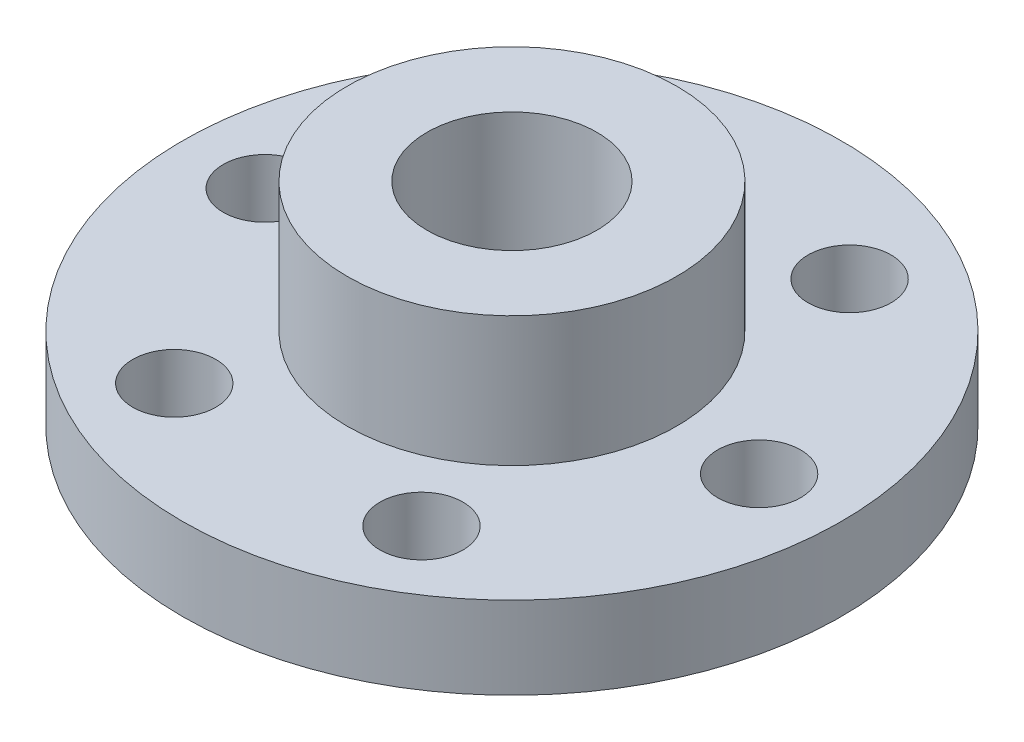
SolidWorks part; units mm, degrees
ref_plane "Front Plane" through (0, 0, 0) normal (0, 0, 1) x (1, 0, 0)
ref_plane "Top Plane" through (0, 0, 0) normal (0, 1, 0) x (1, 0, 0)
ref_plane "Right Plane" through (0, 0, 0) normal (1, 0, 0) x (0, 0, -1)
sketch "Sketch1" plane through (0, 0, 0) normal (0, 1, 0) x (1, 0, 0)
  line L0 (0, 0) -> (6.5484, 0) construction
  line L4 (0, 0) -> (-19.05, 0) construction
  circle A0 centre (0, 0) radius 4.826
  circle A1 centre (0, 0) radius 6.5484 construction
  arc A2 (3.9286, 10.8597) -> (3.9286, -10.8597) centre (0, 0) ccw construction
  circle A3 centre (0, 0) radius 25.4
  circle A5 centre (0, 0) radius 11.5484 construction
  circle A6 centre (-19.05, 0) radius 2.9766 construction
  dimension "D1" = 9.652
  dimension "D2" = 13.0969
  dimension "D3" = 23.0969
  dimension "D7" = 5.9531
  dimension "D5" = 50.8
  dimension "D4" = 19.05
extrude "main body" add sketch "Sketch1" along normal blind 6.35
sketch "Sketch2" plane through (0, 6.35, 0) normal (0, 1, 0) x (1, 0, 0)
  circle A0 centre (0, 0) radius 12.7
  circle A2 centre (0, 0) radius 6.5484
  dimension "D1" = 13.0969
  dimension "D2" = 25.4
extrude "tap boss" add sketch "Sketch2" along normal blind 10
hole_wizard "M6 Clearance Hole1" positions "Sketch3" profile "Sketch4" hole size "M6" standard "ANSI Metric" end condition through all
sketch "Sketch3" plane through (0, 6.35, 0) normal (0, 1, 0) x (1, 0, 0)
  point P0 (-19.05, 0)
  point P7 (-9.525, 16.4978)
  point P8 (9.525, 16.4978)
  point P9 (19.05, 0)
  point P10 (9.525, -16.4978)
  point P11 (-9.525, -16.4978)
  point P12 (0, 0)
  dimension "D1" = 6
sketch "Sketch4" plane through (-19.05, 6.35, 0) normal (1, 0, 0) x (0, 0, 1)
  line L0 (0, 0) -> (0, 6.35)
  line L1 (0, 6.35) -> (3.2, 6.35)
  line L2 (3.2, 6.35) -> (3.2, 0)
  line L5 (3.2, 0) -> (0, 0)
  line L11 (0, -6.35) -> (0, 107.95) construction
  dimension "Thru Hole Dia." = 6.4
  dimension "Thru Hole Depth" = 6.35
sketch "Sketch5" plane through (0, 0, 0) normal (0, -1, 0) x (1, 0, 0)
  line L0 (0, 0) -> (-25.4, 0) construction
  line L1 (-25.4, 0) -> (-25.4, 25.4) construction
  line L2 (-25.4, 25.4) -> (0, 25.4) construction
  line L3 (0, 25.4) -> (0, 0) construction
  circle A0 centre (0, 0) radius 25.4 construction
equation "\"z\" = 8\t\t\t\t'number of blades"
equation "\"de\" = 0.43in\t\t\t'entrance eye diameter"
equation "\"de_length\" = 4mm\t\t'entrance eye consistent length"
equation "\"d_exit\" = 0.18in \t\t'throat aka d1"
equation "\"d2\" = 2.1in \t\t\t'outer diameter of the impeller"
equation "\"b2\" = .2in\t\t\t'tip height from disc surface at d2; slightly higher than d_exit"
equation "\"b1\" = \"b2\" + (\"d2\"/2 - \"de\"/2)*tan(\"theta\") \t\t\t'tip height from disc surface at inlet eye"
equation "\"theta\" = 12\t\t\t'angle of blades from inner to outer "
equation "\"ae\" = 3.14*(\"de\"^2)/4\t\t'entrance eye area'"
equation "\"ce\" = 3.14*\"de\"\t\t'entrance eye circumference"
equation "\"av_ratio\" = .325\t\t'ratio of av/ae at N_s of 470, range is .275 to .375, .325 ideal. High ratio means bigger area means smaller blades"
equation "\"av\" = \"ae\"*\"av_ratio\"\t\t'area between just two blades"
equation "\"s_open\" = \"av\"/\"b1\"\t\t'width of open area"
equation "\"s\"=\"ce\" - \"z\"*\"s_open\""
equation "\"min blade thickness\" = .15in"
equation "\"bearing OD\" = 30mm"
equation "\"bearing ID\"= 10mm"
equation "\"bearing depth\"= 9mm"
equation "\"bearing outer race thickness\"= 1mm"
equation "\"bearing inner race thickness\"= 1mm"
equation "\"bearing bore\" = \"bearing depth\" + 1mm"
equation "\"lower seal OD\" = .917in\t\t'this is https://www.mcmaster.com/#9281k121/=174001b"
equation "\"lower seal ID\"= .375in"
equation "\"lower seal depth\" = .625in + .218in"
equation "\"lower seal bore\" = \"lower seal depth\" + 1mm"
equation "\"upper seal OD\" = 1.125in\t'this is https://www.mcmaster.com/#5154t33/=173zuau, needs to be visually inspected before machining!"
equation "\"upper seal ID\"= 0.625in"
equation "\"upper seal depth\"= .25in\t'aka height; these values need to be confirmed by inspection!! We may want to compress the height."
equation "\"upper seal bore\" = \"upper seal depth\" + 1mm"
equation "\"big o-ring thickness\" = .139in"
equation "\"big o-ring OD\" = 2.734in"
equation "\"big o-ring ID\" = 3.012in"
equation "\"big o-ring groove depth\" = \"big o-ring thickness\"*4/5"
equation "\"impeller center height\" = \"impeller base thickness\" + \"b1\"\t'impeller height at de"
equation "\"impeller outer height\" = \"impeller base thickness\" + \"b2\"\t'impeller height at de"
equation "\"impeller upper clearance\"= .5mm"
equation "\"impeller horizontal clearance\"= (\"d2\"*1.15 - \"d2\")/2 \t\t'clearance based on D2-D3 ratio for circular volute, ranges 1.15 to 1.2"
equation "\"impeller bottom clearance\"= .5mm"
equation "\"impeller base thickness\"= 2mm"
equation "\"impeller dowel diameter\" = 2mm"
equation "\"impeller bolt head diameter\" = \"m4 head bore diameter\""
equation "\"impeller bolt head depth\" = 4mm"
equation "\"impeller bolt stop depth\" = 3mm"
equation "\"impeller bolt bore\" = \"m4 clearance\""
equation "\"impeller shaft bore depth\" = 12mm"
equation "\"impeller shaft bore\" = 8mm"
equation "\"impeller boss depth\" = \"impeller shaft bore depth\"+\"impeller bolt stop depth\"+\"impeller bolt head depth\"-\"impeller base thickness\""
equation "\"impeller boss diameter\" = \"upper seal ID\""
equation "\"impeller dowel length\" = 2mm*2 + \"impeller shaft bore\""
equation "\"coupler motor shaft hole ID\"= 8mm"
equation "\"coupler OD\"= 17mm"
equation "\"coupler length\"= 25mm"
equation "\"motor OD\" = 64mm"
equation "\"motor shaft diameter\"= 8mm"
equation "\"motor shaft pride\"= 32mm"
equation "\"motor to bearing plate distance\" = \"motor shaft pride\" + 2mm +\"coupler length\"/2"
equation "\"square plate bolt bore\" = \"m8 clearance\""
equation "\"square plate bolt head diameter\" = 13.5mm"
equation "\"square plate bolt head depth\" = 8mm"
equation "\"square plate bolt pattern diameter\"= 3.5in"
equation "\"motor mount center bore\"= \"coupler OD\"+ 4mm"
equation "\"motor mount post radius\"= ( 3 * \"square plate bolt bore\" ) / 2"
equation "\"motor mount m4 screw hole diameter\"= 4mm"
equation "\"motor mount m4 head diameter\"= 7.25mm"
equation "\"motor mount m4 head depth\"= 4mm"
equation "\"motor mount m4 pattern diamater\" = 30mm"
equation "\"motor mount plate thickness\"= 8mm + \"motor mount m4 head depth\""
equation "\"bearing plate stop ID\" = \"bearing OD\" - 4mm"
equation "\"bearing plate stop depth\" = 3mm"
equation "\"bearing plate thickness\" = \"bearing bore\" + \"bearing plate stop depth\" + \"shaft bearing stop length\""
equation "\"lower seal plate lip depth\" = 2mm"
equation "\"lower seal plate lip ID\" = \"lower seal OD\" - 3mm"
equation "\"lower seal plate thickness\" = \"lower seal plate lip depth\" + \"lower seal bore\""
equation "\"shaft coupler section diameter\" = 8mm"
equation "\"shaft coupler section length\" = \"motor to bearing plate distance\" - \"motor shaft pride\" - 2mm"
equation "\"shaft bearing section diameter\" = \"bearing ID\""
equation "\"shaft bearing section length\" = \"bearing plate stop depth\" + \"bearing depth\""
equation "\"shaft bearing stop diameter\" = \"bearing ID\" + 4mm"
equation "\"shaft bearing stop length\" = 3mm"
equation "\"shaft lower seal section diameter\" = \"lower seal ID\""
equation "\"shaft lower seal section length\" = \"lower seal plate thickness\" + 1mm"
equation "\"shaft impeller section diameter\" = \"impeller shaft bore\""
equation "\"shaft impeller section length\" = \"upper seal plate thickness\" + \"upper seal plate riser\" + \"impeller bottom clearance\" + \"impeller base thickness\" - \"impeller bolt head depth\" - \"impeller bolt stop depth\""
equation "\"upper seal plate thickness\" = \"upper seal plate pressure hole diameter\"+10mm"
equation "\"upper seal plate lip ID\" = \"upper seal OD\" - 3mm"
equation "\"upper seal plate riser\" = 6.59mm \t\t'this number needs to be read from the housing file"
equation "\"upper seal plate pressure hole diameter\" = .125in\t'this is 1/8 drill "
equation "\"upper seal plate pressure tap diameter\" = .328125in \t'this is 21/64 drill for a 1/8 ANPT tap"
equation "\"upper seal plate pressure tap grip\" = 5mm\t\t'this is the area around the tap so it doesn't crack"
equation "\"upper seal plate pressure tap depth\" = 12mm"
equation "\"impeller cavity center height\"= \"impeller bottom clearance\" + \"impeller upper clearance\" + \"impeller center height\""
equation "\"impeller cavity diameter\"= 2 * \"impeller horizontal clearance\" + \"d2\" \t\t\t\t\t\t\t\t\t'called D3 analytically"
equation "\"impeller cavity outer height\"= \"impeller bottom clearance\" + \"impeller upper clearance\" + \"impeller base thickness\" + \"b2\" \t\t'this is height at impeller diameter d2, not at d3"
equation "\"impeller housing thickness\"= \"impeller housing exit threaded diameter\" + 2*\"impeller housing outlet grip\""
equation "\"impeller housing diameter\" = 4.5in"
equation "\"impeller housing bolt count\" = 8"
equation "\"impeller housing bolt diameter\" = \"m6 clearance\""
equation "\"impeller housing bolt pattern diameter\" = 3.5in"
equation "\"impeller housing threaded inlet diameter\" = 0.71875in \t'this is the 23/32 drill size for 1/2 NPT fitting https://www.mcmaster.com/#50715k269/=176pljy"
equation "\"impeller housing threaded inlet depth\"= .6in"
equation "\"impeller housing exit threaded diameter\"= 0.515625in \t\t'this is the 33/64 drill size for 9/16-18 fitting, expecting swagelok SS-8FK0-1-6STH fitting"
equation "\"impeller housing exit threaded depth\"= 10mm"
equation "\"impeller housing diffuser conical angle\"=10"
equation "\"impeller housing diffuser tangent angle\"=5"
equation "\"impeller housing diffuser final diameter\" = .38in\t\t'aka d2'"
equation "\"impeller housing outlet grip\" = 5mm"
equation "\"end mill size\" = 0.375in\t'for 3/8 endmill"
equation "\"m4 clearance\" = 0.171875in \t'this is 11/64 bit for 4.36mm"
equation "\"m4 tap\" = 0.125in\t\t'this is 1/8 bit for 3.17mm"
equation "\"m4 head bore diameter\" = 7.5mm"
equation "\"m4 head bore depth\" = 5mm\t'actual is ~4mm"
equation "\"m6 clearance\" = 0.234375in\t'this is 15/64 bit = 5.95mm, could use 6mm bit, B bit for 6.04mm or 1/4 bit for 6.35mm"
equation "\"m6 tap\" = 5mm\t\t\t'5mm is appropriate, could use 13/64 or #5,6,7"
equation "\"m6 head bore diameter\" = 11mm\t\t"
equation "\"m6 head bore depth\" = 7mm\t'actual is 6mm"
equation "\"m8 clearance\" = 0.3125in\t'this is 5/16in for 7.93mm, could use 8mm, O,P, or 21/64"
equation "\"m8 tap\" = 0.265625in\t\t'this is 17/64 for 6.746875mm"
equation "\"m8 head bore diameter\" = 14mm"
equation "\"m8 head bore depth\" = 9mm\t'actual is 8mm"
equation "\"D1@Sketch1\"=\"impeller housing diffuser final diameter\""
equation "\"D2@Sketch1\"=\"impeller housing exit threaded diameter\""
equation "\"D3@Sketch1\"=\"impeller housing exit threaded diameter\"+\"impeller housing outlet grip\"*2 "
equation "\"D7@Sketch1\"=\"m6 clearance\""
equation "\"D1@Sketch2\"=\"impeller housing exit threaded diameter\""
equation "\"D1@tap boss\"=10mm"
equation "\"diffuser cartridge OD\" =.75in"
equation "\"diffuser flange bolt pattern diameter\" = 1.4in"
equation "\"D4@Sketch1\"=.75in"
